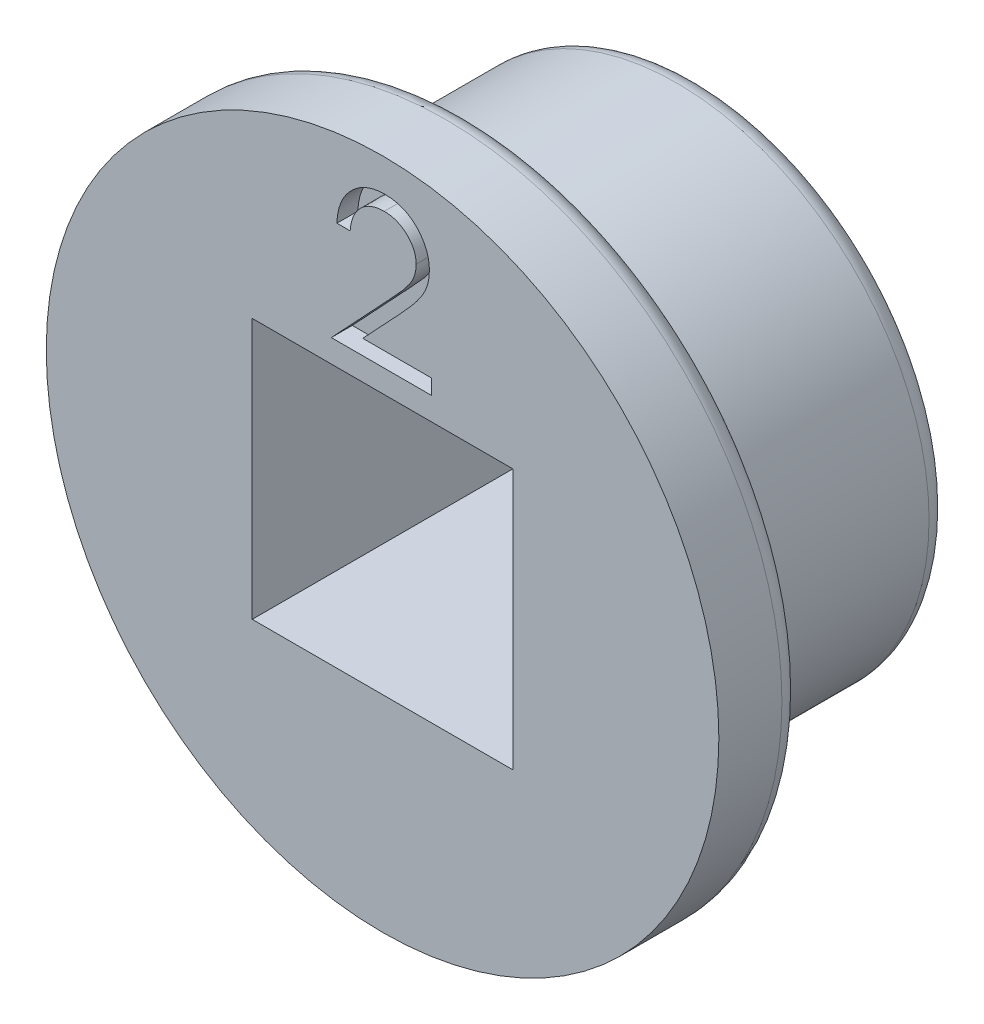
SolidWorks part; units mm, degrees
material "ABS"
ref_plane "Front Plane" through (0, 0, 0) normal (0, 0, 1) x (1, 0, 0)
ref_plane "Top Plane" through (0, 0, 0) normal (0, 1, 0) x (1, 0, 0)
ref_plane "Right Plane" through (0, 0, 0) normal (1, 0, 0) x (0, 0, -1)
sketch "Sketch1" plane through (0, 0, 0) normal (0, 0, 1) x (1, 0, 0)
  line L1 (-3.1, 3.1) -> (3.1, 3.1)
  line L2 (-3.1, 3.1) -> (-3.1, -3.1)
  line L3 (-3.1, -3.1) -> (3.1, -3.1)
  line L4 (3.1, 3.1) -> (3.1, -3.1)
  circle A0 centre (0, 0) radius 6
  circle A1 centre (0, 0) radius 8
  point P4 (0, 3.1)
  point P6 (-3.1, 0)
  dimension "D2" = 12
  dimension "D3" = 16
  dimension "D1" = 6.2
extrude "Boss-Extrude1" add sketch "Sketch1" against normal blind 5.5 contours A0 L1 L4 L3 L2 region at (-5.8303, 0, 0)
extrude "Boss-Extrude2" add sketch "Sketch1<3>" along normal blind 2 contours A1 A0 | A0 L1 L4 L3 L2 region at (-5.8303, 0, 0) region at (-7.7737, 0, 0)
sketch "Sketch1<3>" plane through (0, 0, 0) normal (0, 0, 1) x (1, 0, 0) same geometry as "Sketch1"
fillet "Fillet1" radius 0.5 2 edges at (8, 0, 0) (6, 0, -5.5)
sketch "Sketch2" plane through (0, 0, 2) normal (0, 0, 1) x (1, 0, 0)
  text T0 "2"
extrude "Cut-Extrude1" cut sketch "Sketch2" against normal blind 0.5
